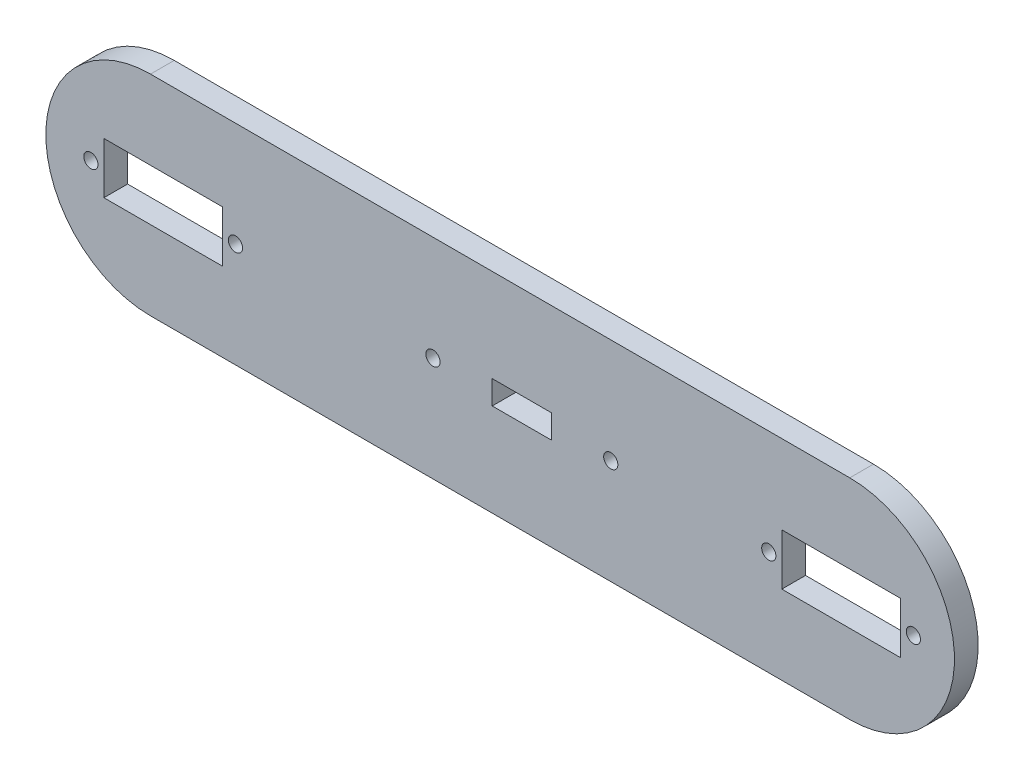
SolidWorks part; units mm, degrees
material "Balsa"
ref_plane "Plano frontal" through (0, 0, 0) normal (0, 0, 1) x (1, 0, 0)
ref_plane "Plano superior" through (0, 0, 0) normal (0, 1, 0) x (1, 0, 0)
ref_plane "Plano direito" through (0, 0, 0) normal (1, 0, 0) x (0, 0, -1)
sketch "Esboço1" plane through (0, 0, 0) normal (0, 0, 1) x (1, 0, 0)
  line L0 (-94, 26.5) -> (83, 26.5)
  line L1 (-94, -26.5) -> (83, -26.5)
  line L2 (-94, 0) -> (-20.7, 0) construction
  line L3 (-22.5, 0) -> (22.5, 0) construction
  line L4 (0, 11.6249) -> (0, -21.7831) construction
  line L6 (-109.1, 0) -> (-72.5, 0) construction
  line L7 (-7.5, -3) -> (7.5, -3)
  line L8 (-7.5, -3) -> (-7.5, 3)
  line L9 (-7.5, 3) -> (7.5, 3)
  line L10 (7.5, -3) -> (7.5, 3)
  line L11 (-7.5, -3) -> (7.5, 3) construction
  line L12 (-7.5, 3) -> (7.5, -3) construction
  line L13 (62.5, 0) -> (99.1, 0) construction
  line L14 (-105.8, -6.5) -> (-75.8, -6.5)
  line L16 (-105.8, 6.5) -> (-75.8, 6.5)
  line L17 (-75.8, -6.5) -> (-75.8, 6.5)
  line L18 (-105.8, -6.5) -> (-75.8, 6.5) construction
  line L19 (-105.8, 6.5) -> (-75.8, -6.5) construction
  line L21 (65.8, -6.5) -> (95.8, -6.5)
  line L22 (65.8, -6.5) -> (65.8, 6.5)
  line L23 (65.8, 6.5) -> (95.8, 6.5)
  line L24 (95.8, -6.5) -> (95.8, 6.5)
  line L25 (65.8, -6.5) -> (95.8, 6.5) construction
  line L26 (65.8, 6.5) -> (95.8, -6.5) construction
  line L27 (-105.8, 6.5) -> (-105.8, -6.5)
  arc A0 (83, -26.5) -> (83, 26.5) centre (83, 0) ccw
  arc A1 (-94, 26.5) -> (-94, -26.5) centre (-94, 0) ccw
  circle A4 centre (-22.5, 0) radius 1.8
  circle A5 centre (22.5, 0) radius 1.8
  circle A6 centre (-109.1, 0) radius 1.8
  circle A7 centre (-72.5, 0) radius 1.8
  circle A8 centre (62.5, 0) radius 1.8
  circle A9 centre (99.1, 0) radius 1.8
  point P8 (0, 0)
  point P19 (0, 0)
  point P24 (0, 0)
  point P29 (-90.8, 0)
  point P34 (80.8, 0)
  point P39 (0, 0)
  point P40 (51.3374, 3.7981)
  point P41 (-96.2887, 6.5)
  point P42 (0, 0)
  point P43 (-103.9311, -6.0199)
  point P44 (20.1799, 0)
  point P45 (23.4434, 0)
  point P46 (0, 0)
  dimension "D1" = 3.6
  dimension "D5" = 15
  dimension "D6" = 26.5
  dimension "D7" = 3.6
  dimension "D2" = 45
  dimension "D3" = 83
  dimension "D4" = 94
  dimension "D8" = 36.6
  dimension "D9" = 50
  dimension "D10" = 6
  dimension "D11" = 13
  dimension "D12" = 30
  dimension "D13" = 40
extrude "Ressalto-extrusão1" add sketch "Esboço1" along normal blind 6
